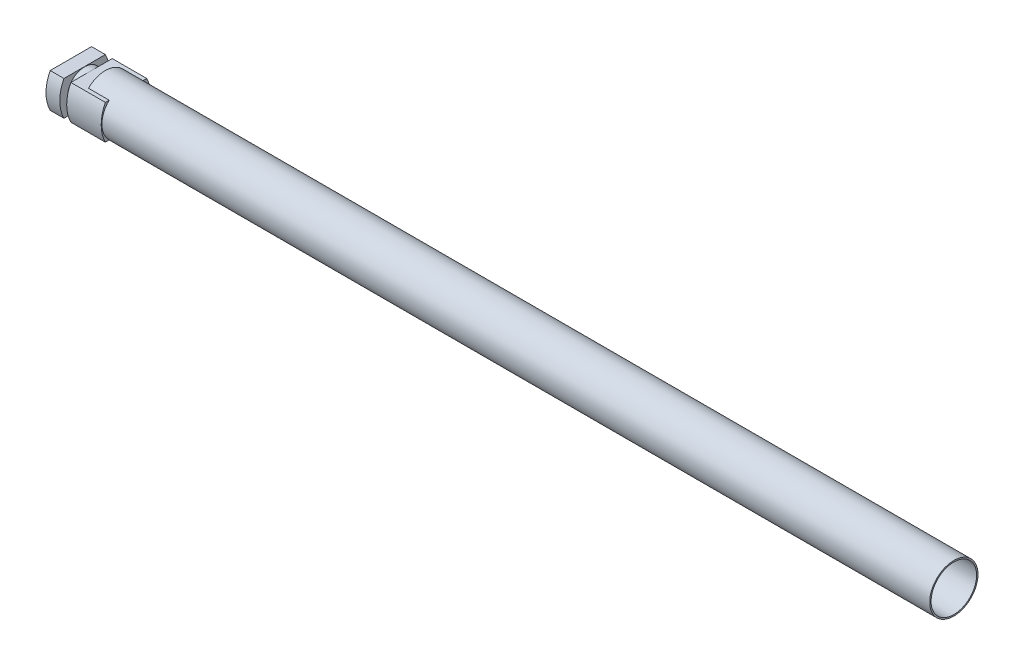
SolidWorks part; units mm, degrees
material "Alloy Steel (SS)"
ref_plane "Front Plane" through (0, 0, 0) normal (0, 0, 1) x (1, 0, 0)
ref_plane "Top Plane" through (0, 0, 0) normal (0, 1, 0) x (1, 0, 0)
ref_plane "Right Plane" through (0, 0, 0) normal (1, 0, 0) x (0, 0, -1)
sketch "Sketch1" plane through (0, 0, 0) normal (1, 0, 0) x (0, 0, -1)
  line L0 (-38.1, 31.75) -> (38.1, 31.75)
  line L4 (38.1, -31.75) -> (-38.1, -31.75)
  arc A2 (-38.1, -31.75) -> (-38.1, 31.75) centre (23.8317, 0) cw
  arc A3 (38.1, 31.75) -> (38.1, -31.75) centre (-23.8317, 0) cw
  point P12 (0, 31.75)
  point P13 (0, -31.75)
  dimension "D2" = 69.596
  dimension "D3" = 76.2
  dimension "D1" = 63.5
  dimension "D4" = 69.596
extrude "Boss-Extrude1" add sketch "Sketch1" along normal blind 101.6
sketch "Sketch2" plane through (0, 0, 0) normal (0, 0, 1) x (1, 0, 0)
  line L0 (-7.219, 0) -> (106.4424, 0) construction
  line L1 (0, 31.75) -> (0, -31.75) construction
  line L2 (25.4, 31.3344) -> (38.1, 31.3344)
  line L3 (25.4, 31.3344) -> (25.4, 56.7344)
  line L4 (25.4, 56.7344) -> (38.1, 56.7344)
  line L5 (38.1, 31.3344) -> (38.1, 56.7344)
  dimension "D1" = 12.7
  dimension "D2" = 25.4
  dimension "D3" = 31.3344
  dimension "D4" = 25.4
revolve "Cut-Revolve1" cut sketch "Sketch2" angle 360 about L0
sketch "Sketch3" plane through (101.6, 0, 0) normal (1, 0, 0) x (0, 0, -1)
  circle A0 centre (0, 0) radius 44.45
  circle A1 centre (0, 0) radius 41.91
  dimension "D2" = 88.9
  dimension "D1" = 2.54
extrude "Boss-Extrude2" add sketch "Sketch3" along normal blind 1524
extrude "Boss-Extrude3" add sketch "Sketch3<2>" against normal blind 38.1
sketch "Sketch3<2>" plane through (101.6, 0, 0) normal (1, 0, 0) x (0, 0, -1) same geometry as "Sketch3"
